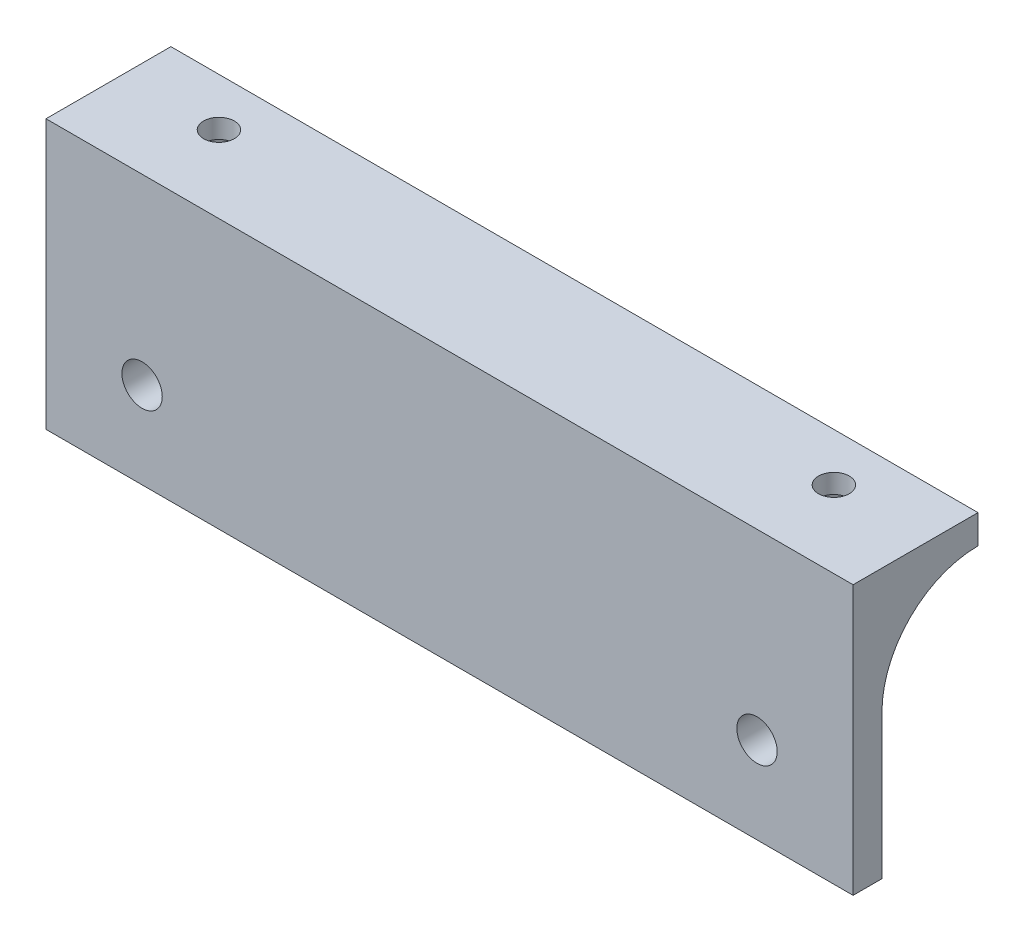
SolidWorks part; units mm, degrees
ref_plane "Front Plane" through (0, 0, 0) normal (0, 0, 1) x (1, 0, 0)
ref_plane "Top Plane" through (0, 0, 0) normal (0, 1, 0) x (1, 0, 0)
ref_plane "Right Plane" through (0, 0, 0) normal (1, 0, 0) x (0, 0, -1)
sketch "Rigidbot" plane through (0, 0, 0) normal (0, 0, 1) x (1, 0, 0)
  line L0 (-42, -5) -> (42, -5) construction
  line L1 (-42, 14) -> (42, 14)
  line L2 (-42, 14) -> (-42, -14)
  line L3 (-42, -14) -> (42, -14)
  line L4 (42, 14) -> (42, -14)
  line L5 (-42, 14) -> (42, -14) construction
  line L6 (-42, -14) -> (42, 14) construction
  line L7 (0, 14) -> (0, -14) construction
  circle A0 centre (-32, -5) radius 2.1
  circle A1 centre (32, -5) radius 2.1
  point P0 (0, 0)
  dimension "D3" = 4.2
  dimension "D1" = 84
  dimension "D2" = 64
  dimension "D4" = 9
  dimension "D5" = 28
extrude "Boss-Rigidbot" add sketch "Rigidbot" along normal blind 3
sketch "Case" plane through (0, 14, 0) normal (0, 1, 0) x (1, 0, 0)
  line L0 (-42, -3) -> (42, -3)
  line L1 (42, -3) -> (42, 10)
  line L2 (42, 10) -> (-42, 10)
  line L3 (-42, 10) -> (-42, -3)
  line L4 (-42, 5) -> (42, 5) construction
  line L5 (0, 10) -> (0, -3) construction
  circle A0 centre (-32, 5) radius 1.6
  circle A1 centre (32, 5) radius 1.6
  dimension "D1" = 3.2
  dimension "D2" = 64
  dimension "D3" = 5
  dimension "D4" = 8
extrude "Boss-Case" add sketch "Case" against normal blind 3
sketch "M3Nut" plane through (0, 14, 0) normal (0, 1, 0) x (1, 0, 0)
  line L0 (0, 10) -> (0, -3) construction
  line L1 (-28.9978, 5) -> (-30.4989, 7.6)
  line L2 (-30.4989, 7.6) -> (-33.5011, 7.6)
  line L3 (-33.5011, 7.6) -> (-35.0022, 5)
  line L4 (-35.0022, 5) -> (-33.5011, 2.4)
  line L5 (-33.5011, 2.4) -> (-30.4989, 2.4)
  line L6 (-30.4989, 2.4) -> (-28.9978, 5)
  line L7 (42, 10) -> (-42, 10) construction
  line L8 (42, -3) -> (-42, -3) construction
  line L9 (30.4989, 2.4) -> (28.9978, 5)
  line L10 (33.5011, 2.4) -> (30.4989, 2.4)
  line L11 (35.0022, 5) -> (33.5011, 2.4)
  line L12 (33.5011, 7.6) -> (35.0022, 5)
  line L13 (30.4989, 7.6) -> (33.5011, 7.6)
  line L14 (28.9978, 5) -> (30.4989, 7.6)
  circle A0 centre (-32, 5) radius 2.6 construction
  circle A1 centre (32, 5) radius 2.6 construction
  dimension "D1" = 5.2
extrude "Cut-M3Nut" cut sketch "M3Nut" against normal blind 10 from offset 2 offset against normal yes
fillet "Fillet" radius 10 1 edges at (0, 11, 0)
